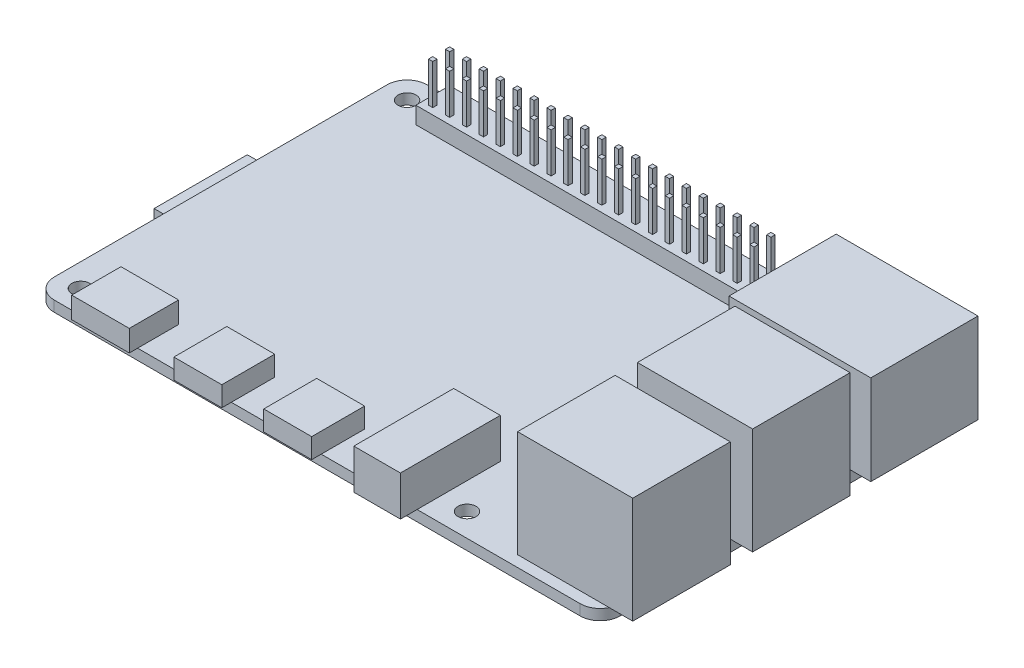
SolidWorks part; units mm, degrees
ref_plane "Front Plane" through (0, 0, 0) normal (0, 0, 1) x (1, 0, 0)
ref_plane "Top Plane" through (0, 0, 0) normal (0, 1, 0) x (1, 0, 0)
ref_plane "Right Plane" through (0, 0, 0) normal (1, 0, 0) x (0, 0, -1)
sketch "Sketch1" plane through (0, 0, 0) normal (0, 1, 0) x (1, 0, 0)
  line L0 (-42.5, 0) -> (42.5, 0) construction
  line L1 (-42.5, -28) -> (42.5, -28)
  line L2 (-42.5, -28) -> (-42.5, 28)
  line L3 (-42.5, 28) -> (42.5, 28)
  line L4 (42.5, -28) -> (42.5, 28)
  line L5 (-42.5, -28) -> (42.5, 28) construction
  line L6 (-42.5, 28) -> (42.5, -28) construction
  circle A0 centre (-39, 24.5) radius 1.35
  circle A1 centre (19, 24.5) radius 1.35
  circle A2 centre (19, -24.5) radius 1.35
  circle A3 centre (-39, -24.5) radius 1.35
  point P0 (0, 0)
  dimension "D3" = 2.7
  dimension "D6" = 2.7
  dimension "D1" = 85
  dimension "D2" = 56
  dimension "D4" = 3.5
  dimension "D5" = 3.5
  dimension "D7" = 3.5
  dimension "D8" = 58
extrude "PCB" add sketch "Sketch1" along normal blind 1.6
fillet "PCB Corners" radius 3 4 edges at (-42.5, 0.8, -28) (42.5, 0.8, -28) (42.5, 0.8, 28) (-42.5, 0.8, 28)
sketch "Connectors" plane through (0, 1.6, 0) normal (0, 1, 0) x (1, 0, 0)
  line L0 (-39, 24.5) -> (19, 24.5) construction
  line L1 (-42.5, 25) -> (-42.5, -25) construction
  line L2 (-35.15, 21.96) -> (15.15, 21.96)
  line L3 (-35.15, 21.96) -> (-35.15, 27.04)
  line L4 (-35.15, 27.04) -> (15.15, 27.04)
  line L5 (15.15, 21.96) -> (15.15, 27.04)
  line L6 (-35.15, 21.96) -> (15.15, 27.04) construction
  line L7 (-35.15, 27.04) -> (15.15, 21.96) construction
  line L8 (24.15, 9.7) -> (45.45, 9.7)
  line L9 (24.15, 9.7) -> (24.15, 25.8)
  line L10 (24.15, 25.8) -> (45.45, 25.8)
  line L11 (45.45, 9.7) -> (45.45, 25.8)
  line L12 (24.15, 9.7) -> (45.45, 25.8) construction
  line L13 (24.15, 25.8) -> (45.45, 9.7) construction
  line L14 (-39.5, -28) -> (39.5, -28) construction
  line L16 (28.419, -8.325) -> (45.719, -8.325)
  line L17 (28.419, -8.325) -> (28.419, 6.325)
  line L18 (28.419, 6.325) -> (45.719, 6.325)
  line L19 (45.719, -8.325) -> (45.719, 6.325)
  line L20 (28.419, -8.325) -> (45.719, 6.325) construction
  line L21 (28.419, 6.325) -> (45.719, -8.325) construction
  line L22 (28.419, -26.325) -> (45.719, -26.325)
  line L23 (28.419, -26.325) -> (28.419, -11.675)
  line L24 (28.419, -11.675) -> (45.719, -11.675)
  line L25 (45.719, -26.325) -> (45.719, -11.675)
  line L26 (28.419, -26.325) -> (45.719, -11.675) construction
  line L27 (28.419, -11.675) -> (45.719, -26.325) construction
  line L28 (-35.625, -29.25) -> (-26.975, -29.25)
  line L29 (-35.625, -29.25) -> (-35.625, -21.85)
  line L30 (-35.625, -21.85) -> (-26.975, -21.85)
  line L31 (-26.975, -29.25) -> (-26.975, -21.85)
  line L32 (-35.625, -29.25) -> (-26.975, -21.85) construction
  line L33 (-35.625, -21.85) -> (-26.975, -29.25) construction
  line L34 (-20.1, -29.43) -> (-12.9, -29.43)
  line L35 (-20.1, -29.43) -> (-20.1, -21.48)
  line L36 (-20.1, -21.48) -> (-12.9, -21.48)
  line L37 (-12.9, -29.43) -> (-12.9, -21.48)
  line L38 (-20.1, -29.43) -> (-12.9, -21.48) construction
  line L39 (-20.1, -21.48) -> (-12.9, -29.43) construction
  line L40 (-6.6, -29.43) -> (0.6, -29.43)
  line L41 (-6.6, -29.43) -> (-6.6, -21.48)
  line L42 (-6.6, -21.48) -> (0.6, -21.48)
  line L43 (0.6, -29.43) -> (0.6, -21.48)
  line L44 (-6.6, -29.43) -> (0.6, -21.48) construction
  line L45 (-6.6, -21.48) -> (0.6, -29.43) construction
  line L46 (8, -30.5) -> (15, -30.5)
  line L47 (8, -30.5) -> (8, -15.5)
  line L48 (8, -15.5) -> (15, -15.5)
  line L49 (15, -30.5) -> (15, -15.5)
  line L50 (8, -30.5) -> (15, -15.5) construction
  line L51 (8, -15.5) -> (15, -30.5) construction
  point P4 (-10, 24.5)
  point P9 (34.8, 17.75)
  point P18 (37.069, -1)
  point P23 (37.069, -19)
  point P28 (-31.3, -25.55)
  point P33 (-16.5, -25.455)
  point P38 (-3, -25.455)
  point P43 (11.5, -23)
  point P49 (-31.3, -21.85)
  line M28 (-39.5, -28) -> (39.5, -28)
  arc M29 (39.5, -28) -> (42.5, -25) centre (39.5, -25) ccw
  line M30 (42.5, -25) -> (42.5, 25)
  arc M31 (42.5, 25) -> (39.5, 28) centre (39.5, 25) ccw
  dimension "D1" = 50.3
  dimension "D2" = 5.08
  dimension "D3" = 21.3
  dimension "D4" = 16.1
  dimension "D5" = 77.3
  dimension "D6" = 45.75
  dimension "D7" = 17.3
  dimension "D8" = 14.65
  dimension "D9" = 27
  dimension "D10" = 79.569
  dimension "D11" = 14.65
  dimension "D12" = 9
  dimension "D13" = 8.65
  dimension "D14" = 11.2
  dimension "D15" = 2.45
  dimension "D16" = 7.4
  dimension "D17" = 7.2
  dimension "D18" = 7.95
  dimension "D19" = 2.545
  dimension "D20" = 14.8
  dimension "D21" = 7.2
  dimension "D22" = 13.5
  dimension "D23" = 7
  dimension "D24" = 15
  dimension "D25" = 5
  dimension "D26" = 14.5
extrude "Ethernet" add sketch "Connectors" along normal blind 13.5 contours L10 L9 L8 M30 M31 | L8 L11 L10 M31 M30 region at (33.3241, 1.6, -17.7492) region at (43.9741, 1.6, -17.7548)
extrude "USB Ports" add sketch "Sketch2<4>" along normal blind 16 contours L18 L17 L16 M30 | L24 L23 L22 M29 M30 | L16 L19 L18 M30 | L22 L25 L24 M30 M29 region at (44.1047, 1.6, 19.0197) region at (35.455, 1.6, 18.9955) region at (44.1095, 1.6, 1) region at (35.4595, 1.6, 1)
sketch "Sketch2<4>" plane through (0, 1.6, 0) normal (0, 1, 0) x (1, 0, 0) same geometry as "Connectors"
extrude "USB C" add sketch "Sketch2<5>" along normal blind 3.2 contours L31 L30 L29 M28 | L28 L31 L29 M28 region at (-31.3, 1.6, 28.625) region at (-31.3, 1.6, 24.925)
sketch "Sketch2<5>" plane through (0, 1.6, 0) normal (0, 1, 0) x (1, 0, 0) same geometry as "Connectors"
extrude "Micro USB" add sketch "Connectors<6>" along normal blind 3 contours L37 L36 L35 M28 | L43 L42 L41 M28 | L34 L37 L35 M28 | L40 L43 L41 M28 region at (-3, 1.6, 24.74) region at (-3, 1.6, 28.715) region at (-16.5, 1.6, 24.74) region at (-16.5, 1.6, 28.715)
sketch "Connectors<6>" plane through (0, 1.6, 0) normal (0, 1, 0) x (1, 0, 0) same geometry as "Connectors"
extrude "Audio Jack" add sketch "Connectors<7>" along normal blind 6 contours L49 L48 L47 M28 | L46 L49 L47 M28 region at (11.5, 1.6, 21.75) region at (11.5, 1.6, 29.25)
sketch "Connectors<7>" plane through (0, 1.6, 0) normal (0, 1, 0) x (1, 0, 0) same geometry as "Connectors"
extrude "Pin Header" add sketch "Connectors<8>" along normal blind 2.54 contours L2 L5 L4 L3 region at (-10, 1.6, -24.5)
sketch "Connectors<8>" plane through (0, 1.6, 0) normal (0, 1, 0) x (1, 0, 0) same geometry as "Connectors"
sketch "Sketch6" plane through (0, 4.14, 0) normal (0, 1, 0) x (1, 0, 0)
  line L0 (-35.15, 27.04) -> (15.15, 27.04) construction
  line L1 (-34.2, 26.09) -> (-33.56, 26.09)
  line L2 (-34.2, 26.09) -> (-34.2, 25.45)
  line L3 (-34.2, 25.45) -> (-33.56, 25.45)
  line L4 (-33.56, 26.09) -> (-33.56, 25.45)
  line L5 (-34.2, 26.09) -> (-33.56, 25.45) construction
  line L6 (-34.2, 25.45) -> (-33.56, 26.09) construction
  line L7 (-35.15, 21.96) -> (-35.15, 27.04) construction
  line L8 (-31.66, 26.09) -> (-31.66, 25.45)
  line L9 (-31.66, 26.09) -> (-31.02, 26.09)
  line L10 (-31.02, 26.09) -> (-31.02, 25.45)
  line L11 (-31.66, 25.45) -> (-31.02, 25.45)
  line L12 (-29.12, 26.09) -> (-29.12, 25.45)
  line L13 (-29.12, 26.09) -> (-28.48, 26.09)
  line L14 (-28.48, 26.09) -> (-28.48, 25.45)
  line L15 (-29.12, 25.45) -> (-28.48, 25.45)
  line L16 (-26.58, 26.09) -> (-26.58, 25.45)
  line L17 (-26.58, 26.09) -> (-25.94, 26.09)
  line L18 (-25.94, 26.09) -> (-25.94, 25.45)
  line L19 (-26.58, 25.45) -> (-25.94, 25.45)
  line L20 (-24.04, 26.09) -> (-24.04, 25.45)
  line L21 (-24.04, 26.09) -> (-23.4, 26.09)
  line L22 (-23.4, 26.09) -> (-23.4, 25.45)
  line L23 (-24.04, 25.45) -> (-23.4, 25.45)
  line L24 (-21.5, 26.09) -> (-21.5, 25.45)
  line L25 (-21.5, 26.09) -> (-20.86, 26.09)
  line L26 (-20.86, 26.09) -> (-20.86, 25.45)
  line L27 (-21.5, 25.45) -> (-20.86, 25.45)
  line L28 (-18.96, 26.09) -> (-18.96, 25.45)
  line L29 (-18.96, 26.09) -> (-18.32, 26.09)
  line L30 (-18.32, 26.09) -> (-18.32, 25.45)
  line L31 (-18.96, 25.45) -> (-18.32, 25.45)
  line L32 (-16.42, 26.09) -> (-16.42, 25.45)
  line L33 (-16.42, 26.09) -> (-15.78, 26.09)
  line L34 (-15.78, 26.09) -> (-15.78, 25.45)
  line L35 (-16.42, 25.45) -> (-15.78, 25.45)
  line L36 (-13.88, 26.09) -> (-13.88, 25.45)
  line L37 (-13.88, 26.09) -> (-13.24, 26.09)
  line L38 (-13.24, 26.09) -> (-13.24, 25.45)
  line L39 (-13.88, 25.45) -> (-13.24, 25.45)
  line L40 (-11.34, 26.09) -> (-11.34, 25.45)
  line L41 (-11.34, 26.09) -> (-10.7, 26.09)
  line L42 (-10.7, 26.09) -> (-10.7, 25.45)
  line L43 (-11.34, 25.45) -> (-10.7, 25.45)
  line L44 (-8.8, 26.09) -> (-8.8, 25.45)
  line L45 (-8.8, 26.09) -> (-8.16, 26.09)
  line L46 (-8.16, 26.09) -> (-8.16, 25.45)
  line L47 (-8.8, 25.45) -> (-8.16, 25.45)
  line L48 (-6.26, 26.09) -> (-6.26, 25.45)
  line L49 (-6.26, 26.09) -> (-5.62, 26.09)
  line L50 (-5.62, 26.09) -> (-5.62, 25.45)
  line L51 (-6.26, 25.45) -> (-5.62, 25.45)
  line L52 (-3.72, 26.09) -> (-3.72, 25.45)
  line L53 (-3.72, 26.09) -> (-3.08, 26.09)
  line L54 (-3.08, 26.09) -> (-3.08, 25.45)
  line L55 (-3.72, 25.45) -> (-3.08, 25.45)
  line L56 (-1.18, 26.09) -> (-1.18, 25.45)
  line L57 (-1.18, 26.09) -> (-0.54, 26.09)
  line L58 (-0.54, 26.09) -> (-0.54, 25.45)
  line L59 (-1.18, 25.45) -> (-0.54, 25.45)
  line L60 (1.36, 26.09) -> (1.36, 25.45)
  line L61 (1.36, 26.09) -> (2, 26.09)
  line L62 (2, 26.09) -> (2, 25.45)
  line L63 (1.36, 25.45) -> (2, 25.45)
  line L64 (3.9, 26.09) -> (3.9, 25.45)
  line L65 (3.9, 26.09) -> (4.54, 26.09)
  line L66 (4.54, 26.09) -> (4.54, 25.45)
  line L67 (3.9, 25.45) -> (4.54, 25.45)
  line L68 (6.44, 26.09) -> (6.44, 25.45)
  line L69 (6.44, 26.09) -> (7.08, 26.09)
  line L70 (7.08, 26.09) -> (7.08, 25.45)
  line L71 (6.44, 25.45) -> (7.08, 25.45)
  line L72 (8.98, 26.09) -> (8.98, 25.45)
  line L73 (8.98, 26.09) -> (9.62, 26.09)
  line L74 (9.62, 26.09) -> (9.62, 25.45)
  line L75 (8.98, 25.45) -> (9.62, 25.45)
  line L76 (11.52, 26.09) -> (11.52, 25.45)
  line L77 (11.52, 26.09) -> (12.16, 26.09)
  line L78 (12.16, 26.09) -> (12.16, 25.45)
  line L79 (11.52, 25.45) -> (12.16, 25.45)
  line L80 (14.06, 26.09) -> (14.06, 25.45)
  line L81 (14.06, 26.09) -> (14.7, 26.09)
  line L82 (14.7, 26.09) -> (14.7, 25.45)
  line L83 (14.06, 25.45) -> (14.7, 25.45)
  line L84 (-31.66, 23.55) -> (-31.66, 22.91)
  line L85 (-31.66, 23.55) -> (-31.02, 23.55)
  line L86 (-31.02, 23.55) -> (-31.02, 22.91)
  line L87 (-31.66, 22.91) -> (-31.02, 22.91)
  line L88 (-29.12, 23.55) -> (-29.12, 22.91)
  line L89 (-29.12, 23.55) -> (-28.48, 23.55)
  line L90 (-28.48, 23.55) -> (-28.48, 22.91)
  line L91 (-29.12, 22.91) -> (-28.48, 22.91)
  line L92 (-26.58, 23.55) -> (-26.58, 22.91)
  line L93 (-26.58, 23.55) -> (-25.94, 23.55)
  line L94 (-25.94, 23.55) -> (-25.94, 22.91)
  line L95 (-26.58, 22.91) -> (-25.94, 22.91)
  line L96 (-24.04, 23.55) -> (-24.04, 22.91)
  line L97 (-24.04, 23.55) -> (-23.4, 23.55)
  line L98 (-23.4, 23.55) -> (-23.4, 22.91)
  line L99 (-24.04, 22.91) -> (-23.4, 22.91)
  line L100 (-21.5, 23.55) -> (-21.5, 22.91)
  line L101 (-21.5, 23.55) -> (-20.86, 23.55)
  line L102 (-20.86, 23.55) -> (-20.86, 22.91)
  line L103 (-21.5, 22.91) -> (-20.86, 22.91)
  line L104 (-18.96, 23.55) -> (-18.96, 22.91)
  line L105 (-18.96, 23.55) -> (-18.32, 23.55)
  line L106 (-18.32, 23.55) -> (-18.32, 22.91)
  line L107 (-18.96, 22.91) -> (-18.32, 22.91)
  line L108 (-16.42, 23.55) -> (-16.42, 22.91)
  line L109 (-16.42, 23.55) -> (-15.78, 23.55)
  line L110 (-15.78, 23.55) -> (-15.78, 22.91)
  line L111 (-16.42, 22.91) -> (-15.78, 22.91)
  line L112 (-13.88, 23.55) -> (-13.88, 22.91)
  line L113 (-13.88, 23.55) -> (-13.24, 23.55)
  line L114 (-13.24, 23.55) -> (-13.24, 22.91)
  line L115 (-13.88, 22.91) -> (-13.24, 22.91)
  line L116 (-11.34, 23.55) -> (-11.34, 22.91)
  line L117 (-11.34, 23.55) -> (-10.7, 23.55)
  line L118 (-10.7, 23.55) -> (-10.7, 22.91)
  line L119 (-11.34, 22.91) -> (-10.7, 22.91)
  line L120 (-8.8, 23.55) -> (-8.8, 22.91)
  line L121 (-8.8, 23.55) -> (-8.16, 23.55)
  line L122 (-8.16, 23.55) -> (-8.16, 22.91)
  line L123 (-8.8, 22.91) -> (-8.16, 22.91)
  line L124 (-6.26, 23.55) -> (-6.26, 22.91)
  line L125 (-6.26, 23.55) -> (-5.62, 23.55)
  line L126 (-5.62, 23.55) -> (-5.62, 22.91)
  line L127 (-6.26, 22.91) -> (-5.62, 22.91)
  line L128 (-3.72, 23.55) -> (-3.72, 22.91)
  line L129 (-3.72, 23.55) -> (-3.08, 23.55)
  line L130 (-3.08, 23.55) -> (-3.08, 22.91)
  line L131 (-3.72, 22.91) -> (-3.08, 22.91)
  line L132 (-1.18, 23.55) -> (-1.18, 22.91)
  line L133 (-1.18, 23.55) -> (-0.54, 23.55)
  line L134 (-0.54, 23.55) -> (-0.54, 22.91)
  line L135 (-1.18, 22.91) -> (-0.54, 22.91)
  line L136 (1.36, 23.55) -> (1.36, 22.91)
  line L137 (1.36, 23.55) -> (2, 23.55)
  line L138 (2, 23.55) -> (2, 22.91)
  line L139 (1.36, 22.91) -> (2, 22.91)
  line L140 (3.9, 23.55) -> (3.9, 22.91)
  line L141 (3.9, 23.55) -> (4.54, 23.55)
  line L142 (4.54, 23.55) -> (4.54, 22.91)
  line L143 (3.9, 22.91) -> (4.54, 22.91)
  line L144 (6.44, 23.55) -> (6.44, 22.91)
  line L145 (6.44, 23.55) -> (7.08, 23.55)
  line L146 (7.08, 23.55) -> (7.08, 22.91)
  line L147 (6.44, 22.91) -> (7.08, 22.91)
  line L148 (8.98, 23.55) -> (8.98, 22.91)
  line L149 (8.98, 23.55) -> (9.62, 23.55)
  line L150 (9.62, 23.55) -> (9.62, 22.91)
  line L151 (8.98, 22.91) -> (9.62, 22.91)
  line L152 (11.52, 23.55) -> (11.52, 22.91)
  line L153 (11.52, 23.55) -> (12.16, 23.55)
  line L154 (12.16, 23.55) -> (12.16, 22.91)
  line L155 (11.52, 22.91) -> (12.16, 22.91)
  line L156 (14.06, 23.55) -> (14.06, 22.91)
  line L157 (14.06, 23.55) -> (14.7, 23.55)
  line L158 (14.7, 23.55) -> (14.7, 22.91)
  line L159 (14.06, 22.91) -> (14.7, 22.91)
  line L160 (-34.2, 23.55) -> (-34.2, 22.91)
  line L161 (-34.2, 23.55) -> (-33.56, 23.55)
  line L162 (-33.56, 23.55) -> (-33.56, 22.91)
  line L163 (-34.2, 22.91) -> (-33.56, 22.91)
  point P0 (-33.88, 25.77)
  dimension "D1" = 1.27
  dimension "D2" = 1.27
  dimension "D3" = 0.64
  dimension "D4" = 0.64
  dimension "D5" = 20
  dimension "D6" = 2
extrude "Pin Header Pins" add sketch "Sketch6" along normal blind 6
sketch "Sketch7" plane through (0, 0, 0) normal (0, -1, 0) x (1, 0, 0)
  line L1 (-45.5, -7) -> (-28.5, -7)
  line L2 (-45.5, -7) -> (-45.5, 7)
  line L3 (-45.5, 7) -> (-28.5, 7)
  line L4 (-28.5, -7) -> (-28.5, 7)
  line L5 (-45.5, -7) -> (-28.5, 7) construction
  line L6 (-45.5, 7) -> (-28.5, -7) construction
  line L7 (-42.5, -25) -> (-42.5, 25) construction
  line L12 (-39.5, 28) -> (39.5, 28) construction
  line L13 (39.5, -28) -> (-39.5, -28) construction
  point P0 (-37, 0)
  dimension "D1" = 21
  dimension "D2" = 14
  dimension "D3" = 17
  dimension "D4" = 3
  dimension "D5" = 21
extrude "Boss-Extrude1" add sketch "Sketch7" along normal blind 2
